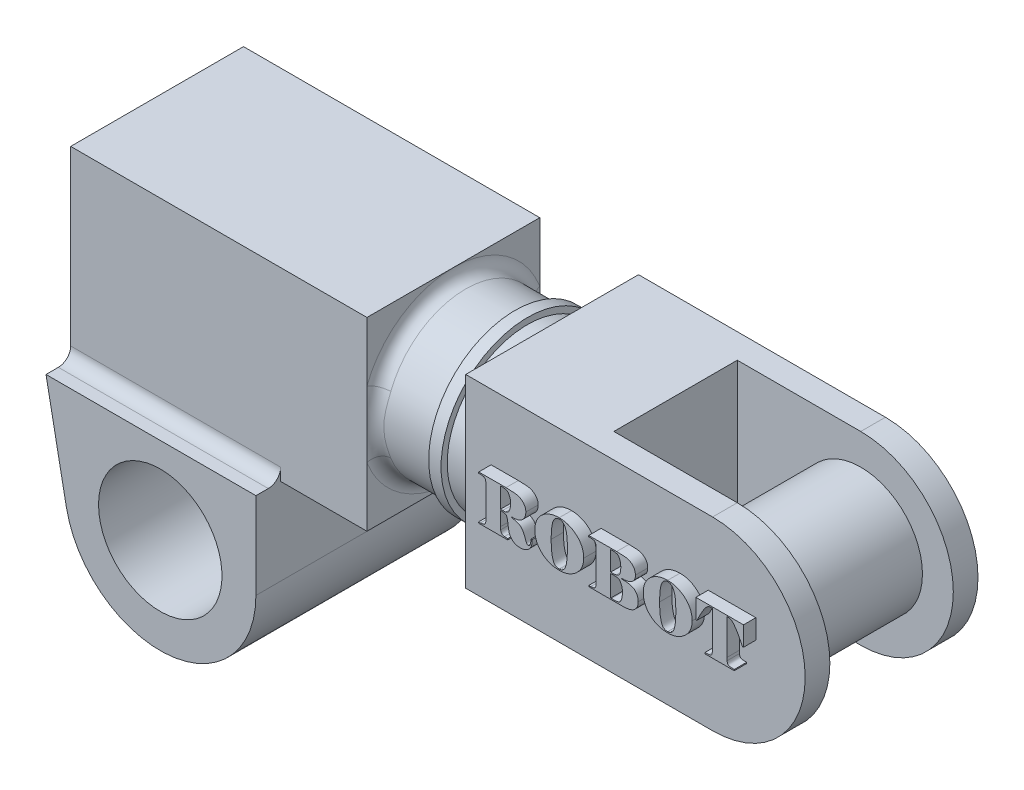
SolidWorks part; units mm, degrees
ref_plane "Front Plane" through (0, 0, 0) normal (0, 0, 1) x (1, 0, 0)
ref_plane "Top Plane" through (0, 0, 0) normal (0, 1, 0) x (1, 0, 0)
ref_plane "Right Plane" through (0, 0, 0) normal (1, 0, 0) x (0, 0, -1)
sketch "Sketch1" plane through (0, 0, 0) normal (1, 0, 0) x (0, 0, -1)
  line L1 (-70, 75) -> (70, 75)
  line L2 (-70, 75) -> (-70, -75)
  line L3 (-70, -75) -> (70, -75)
  line L4 (70, 75) -> (70, -75)
  line L5 (-70, 75) -> (70, -75) construction
  line L6 (-70, -75) -> (70, 75) construction
  point P0 (0, 0)
  dimension "D1" = 150
  dimension "D2" = 140
extrude "Boss-Extrude1" add sketch "Sketch1" along normal blind 240
sketch "Sketch2" plane through (240, 0, 0) normal (1, 0, 0) x (0, 0, -1)
  circle A0 centre (0, 0) radius 65
  dimension "D1" = 130
extrude "Boss-Extrude2" add sketch "Sketch2" along normal blind 50
sketch "Sketch3" plane through (290, 0, 0) normal (1, 0, 0) x (0, 0, -1)
  circle A0 centre (0, 0) radius 70
  dimension "D1" = 140
extrude "Boss-Extrude3" add sketch "Sketch3" along normal blind 10
sketch "Sketch4" plane through (0, 0, 0) normal (0, 0, 1) x (1, 0, 0)
  line L0 (0, -75) -> (16.5223, -160)
  line L1 (0, 75) -> (0, -75) construction
  line L2 (170.0569, -145) -> (170.0569, -75)
  line L3 (240, -75) -> (0, -75) construction
  line L4 (0, -75) -> (170.0569, -75)
  arc A0 (16.5223, -160) -> (170.0569, -145) centre (92.5569, -145) ccw
  circle A1 centre (92.5569, -145) radius 50
  dimension "D1" = 155
  dimension "D2" = 100
  dimension "D3" = 191
  dimension "D4" = 85
  dimension "D5" = 70
extrude "Boss-Extrude4" add sketch "Sketch4" along normal mid plane 180
fillet "Fillet1" radius 10 3 edges at (85.0284, -75, -70) (240, 0, -65) (85.0284, -75, 70)
sketch "Sketch5" plane through (300, 0, 0) normal (1, 0, 0) x (0, 0, -1)
  circle A0 centre (0, 0) radius 65
  dimension "D1" = 130
extrude "Boss-Extrude5" add sketch "Sketch5" along normal blind 20
sketch "Sketch6" plane through (0, 0, 0) normal (0, 0, 1) x (1, 0, 0)
  line L0 (520, 75) -> (320, 75)
  line L2 (320, 75) -> (320, -75)
  line L3 (320, -75) -> (520, -75)
  line L4 (320, -65) -> (320, 65) construction
  arc A0 (520, -75) -> (520, 75) centre (520, 0) ccw
  dimension "D1" = 150
  dimension "D2" = 200
extrude "Boss-Extrude6" add sketch "Sketch6" along normal mid plane 140
sketch "Sketch7" plane through (0, 0, 0) normal (0, 0, 1) x (1, 0, 0)
  line L0 (520, 75) -> (420, 75)
  line L1 (520, 75) -> (320, 75) construction
  line L2 (420, 75) -> (420, -75)
  line L3 (320, -75) -> (520, -75) construction
  line L4 (420, -75) -> (520, -75)
  arc A0 (520, -75) -> (520, 75) centre (520, 0) ccw construction
  arc A1 (520, -75) -> (520, 75) centre (520, 0) ccw
extrude "Cut-Extrude1" cut sketch "Sketch7" against normal mid plane 100
sketch "Sketch9" plane through (0, 0, -50) normal (0, 0, 1) x (1, 0, 0)
  circle A0 centre (520, 0) radius 50
  dimension "D1" = 100
extrude "Boss-Extrude7" add sketch "Sketch9" along normal blind 100
sketch "Sketch10" plane through (0, 0, 70) normal (0, 0, 1) x (1, 0, 0)
  text T0 "ROBOT" font "Elephant" height in points 140
extrude "Boss-Extrude8" add sketch "Sketch10" along normal blind 10
